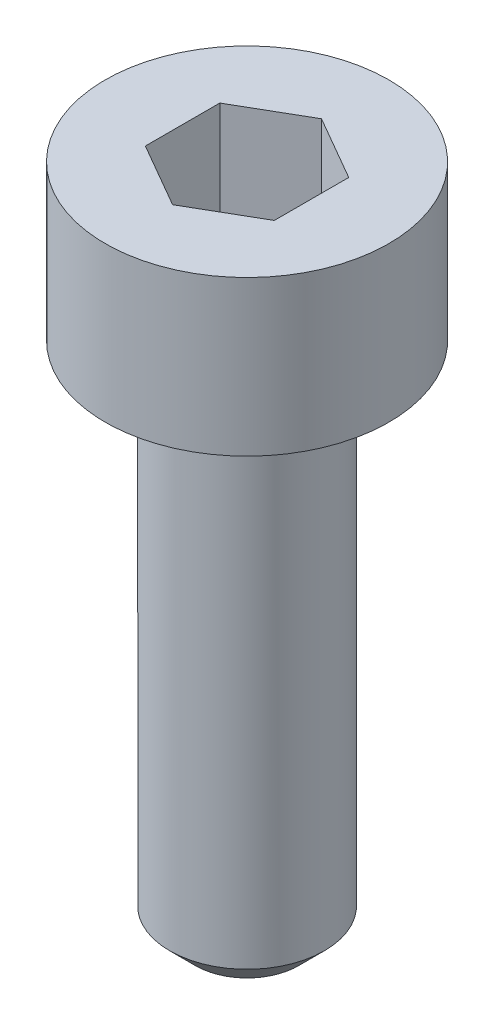
SolidWorks part; units mm, degrees
ref_plane "Front Plane" through (0, 0, 0) normal (0, 0, 1) x (1, 0, 0)
ref_plane "Top Plane" through (0, 0, 0) normal (0, 1, 0) x (1, 0, 0)
ref_plane "Right Plane" through (0, 0, 0) normal (1, 0, 0) x (0, 0, -1)
sketch "Sketch1" plane through (0, 0, 0) normal (0, 0, 1) x (1, 0, 0)
  line L0 (0, 13) -> (-2.75, 13)
  line L1 (-2.75, 13) -> (-2.75, 10)
  line L2 (-2.75, 10) -> (-1.5, 10)
  line L3 (-1.5, 10) -> (-1.5, 0)
  line L4 (-1.5, 0) -> (0, 0)
  line L5 (0, 0) -> (0, 13)
  dimension "D1" = 1.5
  dimension "D2" = 10
  dimension "D3" = 3
  dimension "D4" = 2.75
revolve "Revolve1" add sketch "Sketch1" angle 360 about L5
sketch "Sketch2" plane through (0, 13, 0) normal (0, 1, 0) x (1, 0, 0)
  line L1 (0, 1.4434) -> (-1.25, 0.7217)
  line L2 (-1.25, 0.7217) -> (-1.25, -0.7217)
  line L3 (-1.25, -0.7217) -> (0, -1.4434)
  line L4 (0, -1.4434) -> (1.25, -0.7217)
  line L5 (1.25, -0.7217) -> (1.25, 0.7217)
  line L6 (1.25, 0.7217) -> (0, 1.4434)
  circle A0 centre (0, 0) radius 1.25 construction
  dimension "D1" = 2.5
extrude "Под шестигранник" cut sketch "Sketch2" against normal blind 2
chamfer "Chamfer1" distance 0.5 angle 45 1 edges at (0, 0, -1.5)
